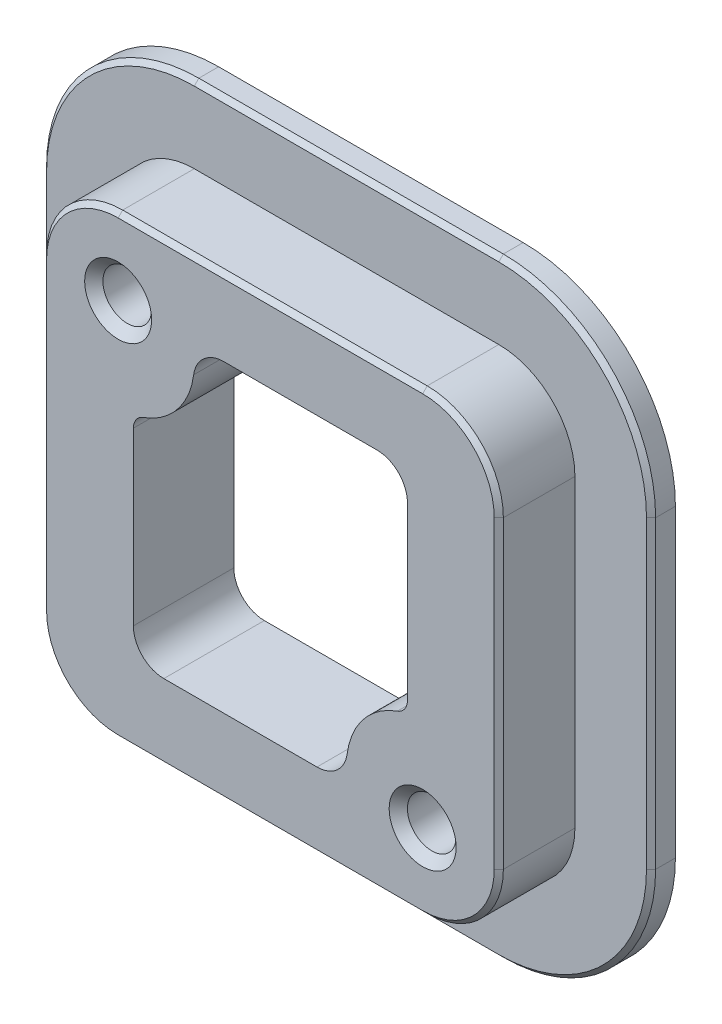
SolidWorks part; units mm, degrees
ref_plane "Ebene vorne" through (0, 0, 0) normal (0, 0, 1) x (1, 0, 0)
ref_plane "Ebene oben" through (0, 0, 0) normal (0, 1, 0) x (1, 0, 0)
ref_plane "Ebene rechts" through (0, 0, 0) normal (1, 0, 0) x (0, 0, -1)
sketch "Skizze1" plane through (0, 0, 0) normal (0, 0, 1) x (1, 0, 0)
  line L1 (15, 15) -> (-15, 15)
  line L2 (15, 15) -> (15, -15)
  line L3 (15, -15) -> (-15, -15)
  line L4 (-15, 15) -> (-15, -15)
  line L5 (15, 15) -> (-15, -15) construction
  line L6 (15, -15) -> (-15, 15) construction
  point P0 (0, 0)
  dimension "D1" = 30
  dimension "D2" = 30
extrude "Grundkörper" add sketch "Skizze1" along normal blind 5
fillet "Verrundung1" radius 5 4 edges at (-15, 15, 2.5) (-15, -15, 2.5) (15, -15, 2.5) (15, 15, 2.5)
sketch "Skizze2" plane through (0, 0, 0) normal (0, 0, -1) x (-1, 0, 0)
  line L8 (20, -10) -> (20, 10)
  line L9 (10, 20) -> (-10, 20)
  line L10 (-20, 10) -> (-20, -10)
  line L11 (-10, -20) -> (10, -20)
  line L12 (20, -10) -> (20, 10)
  line L13 (10, 20) -> (-10, 20)
  line L14 (-20, 10) -> (-20, -10)
  line L15 (-10, -20) -> (10, -20)
  arc A8 (20, 10) -> (10, 20) centre (10, 10) ccw
  arc A9 (-10, 20) -> (-20, 10) centre (-10, 10) ccw
  arc A10 (-20, -10) -> (-10, -20) centre (-10, -10) ccw
  arc A11 (10, -20) -> (20, -10) centre (10, -10) ccw
  arc A12 (20, 10) -> (10, 20) centre (10, 10) ccw
  arc A13 (-10, 20) -> (-20, 10) centre (-10, 10) ccw
  arc A14 (-20, -10) -> (-10, -20) centre (-10, -10) ccw
  arc A15 (10, -20) -> (20, -10) centre (10, -10) ccw
  dimension "D1" = 5
extrude "Absatz" add sketch "Skizze2" along normal blind 1.6
sketch "Skizze3" plane through (0, 0, 5) normal (0, 0, 1) x (1, 0, 0)
  circle A0 centre (-10, 10) radius 1.6
  circle A1 centre (10, -10) radius 1.6
  dimension "D1" = 3.2
extrude "M3 Bohrungen" cut sketch "Skizze3" against normal through all
sketch "Skizze4" plane through (0, 0, -1.6) normal (0, 0, -1) x (-1, 0, 0)
  line L1 (10, 6.5359) -> (13, 8.2679)
  line L2 (13, 8.2679) -> (13, 11.7321)
  line L3 (13, 11.7321) -> (10, 13.4641)
  line L4 (10, 13.4641) -> (7, 11.7321)
  line L5 (7, 11.7321) -> (7, 8.2679)
  line L6 (7, 8.2679) -> (10, 6.5359)
  line L7 (-10, -6.5359) -> (-13, -8.2679)
  line L8 (-13, -8.2679) -> (-13, -11.7321)
  line L9 (-13, -11.7321) -> (-10, -13.4641)
  line L10 (-10, -13.4641) -> (-7, -11.7321)
  line L11 (-7, -11.7321) -> (-7, -8.2679)
  line L12 (-7, -8.2679) -> (-10, -6.5359)
  circle A0 centre (10, 10) radius 3 construction
  circle A1 centre (-10, -10) radius 3 construction
  dimension "D1" = 6
extrude "M3 Schskant" cut sketch "Skizze4" against normal blind 3
sketch "Skizze5" plane through (0, 0, 5) normal (0, 0, 1) x (1, 0, 0)
  line L1 (5, 10) -> (-5, 10)
  line L2 (5, -4) -> (5, -10)
  line L3 (5, -10) -> (-5, -10)
  line L4 (-5, 10) -> (-5, 4)
  line L5 (5, 10) -> (-5, -10) construction
  line L6 (5, -10) -> (-5, 10) construction
  line L7 (-5, -10) -> (-9, -10)
  line L9 (-5, 4) -> (-9, 4)
  line L10 (-9, -10) -> (-9, 4)
  line L11 (5, 10) -> (9, 10)
  line L13 (5, -4) -> (9, -4)
  line L14 (9, 10) -> (9, -4)
  point P0 (0, 0)
  dimension "D1" = 20
  dimension "D2" = 10
  dimension "D3" = 4
  dimension "D4" = 14
extrude "Durchbruch" cut sketch "Skizze5" against normal through all
fillet "Verrundung2" radius 5 2 edges at (5, -4, 1.7) (-5, 4, 1.7)
fillet "Verrundung3" radius 2 4 edges at (5, -10, 1.7) (-9, -10, 1.7) (-5, 10, 1.7) (9, 10, 1.7)
fillet "Verrundung4" radius 1 2 edges at (9, -4, 1.7) (-9, 4, 1.7)
chamfer "Fase1" distance 0.3 angle 45 16 edges at (0, -20, 0) (-17.0711, -17.0711, 0) (17.0711, -17.0711, 0) (-20, 0, 0) (20, 0, 0) (-17.0711, 17.0711, 0) (17.0711, 17.0711, 0) (0, 20, 0) (0, -15, 5) (13.5355, -13.5355, 5) (-13.5355, -13.5355, 5) (15, 0, 5) (-15, 0, 5) (13.5355, 13.5355, 5) (-13.5355, 13.5355, 5) (0, 15, 5)
chamfer "Fase2" distance 0.6 angle 45 2 edges at (-8.4, 10, 5) (11.6, -10, 5)
